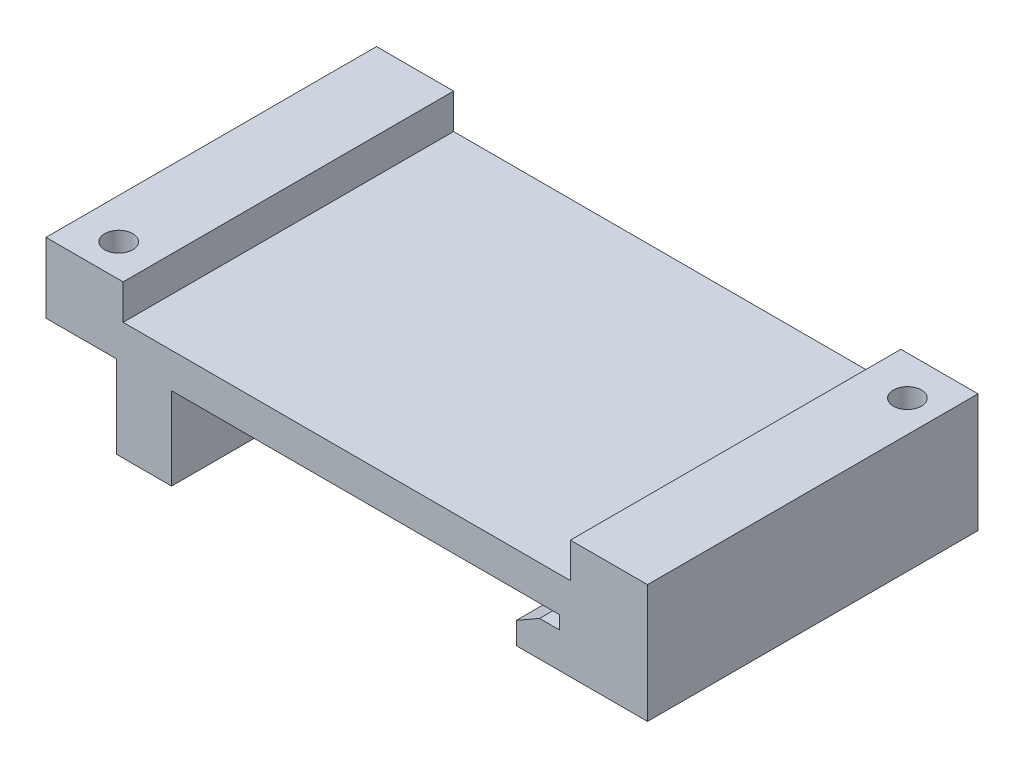
SolidWorks part; units mm, degrees
ref_plane "Front Plane" through (0, 0, 0) normal (0, 0, 1) x (1, 0, 0)
ref_plane "Top Plane" through (0, 0, 0) normal (0, 1, 0) x (1, 0, 0)
ref_plane "Right Plane" through (0, 0, 0) normal (1, 0, 0) x (0, 0, -1)
sketch "Sketch1" plane through (0, 0, 0) normal (0, 0, 1) x (1, 0, 0)
  line L0 (0, 0) -> (19.3, 0)
  line L1 (19.3, 0) -> (19.3, -1.2)
  line L2 (19.3, -1.2) -> (17.5, -1.2)
  line L3 (17.5, -1.2) -> (15.4, -2.4)
  line L4 (15.4, -2.4) -> (15.4, -4.4)
  line L5 (15.4, -4.4) -> (27.3, -4.4)
  line L8 (20.3, 3.175) -> (-20.3, 3.175)
  line L10 (-20.9, -7.5) -> (-15.9, -7.5)
  line L11 (-15.9, -7.5) -> (-15.9, 0)
  line L12 (-15.9, 0) -> (0, 0)
  line L14 (-27.3, 6.355) -> (-20.3, 6.355)
  line L15 (-20.3, 6.355) -> (-20.3, 3.175)
  line L16 (0, 0) -> (0, 6.355) construction
  line L18 (27.3, 6.355) -> (20.3, 6.355)
  line L19 (20.3, 6.355) -> (20.3, 3.175)
  line L20 (27.3, 6.355) -> (27.3, -4.4)
  line L21 (-27.3, 6.355) -> (-27.3, 0)
  line L22 (-27.3, 0) -> (-20.9, 0)
  line L23 (-20.9, 0) -> (-20.9, -7.5)
  dimension "D2" = 1.8
  dimension "D3" = 3.9
  dimension "D4" = 3.2
  dimension "D5" = 1.2
  dimension "D6" = 1.2
  dimension "D7" = 5
  dimension "D8" = 7.5
  dimension "D9" = 3.175
  dimension "D10" = 15.4
  dimension "D11" = 54.6
  dimension "D12" = 7
  dimension "D13" = 3.18
  dimension "D14" = 15.9
extrude "Boss-Extrude1" add sketch "Sketch1" along normal blind 30
sketch "Sketch2" plane through (-20.9, 0, 0) normal (-1, 0, 0) x (0, 0, 1)
  line L0 (15, 0) -> (15, -7.5) construction
  line L1 (30, 0) -> (0, 0) construction
  line L2 (30, -7.5) -> (0, -7.5) construction
  line L3 (0, 0) -> (15, 0) construction
  line L4 (7.5, 0) -> (7.5, -7.5) construction
  line L5 (15, 0) -> (30, 0) construction
  line L6 (22.5, 0) -> (22.5, -7.5) construction
  circle A0 centre (7.5, -3.75) radius 1.275
  circle A1 centre (22.5, -3.75) radius 1.275
  point P10 (15, -3.75)
  dimension "D1" = 2.55
extrude "Cut-Extrude1" cut sketch "Sketch2" against normal up to surface (5 mm away) up to face at (-15.9, -3.75, 15)
sketch "Sketch3" plane through (0, 6.355, 0) normal (0, 1, 0) x (1, 0, 0)
  line L1 (-27.3, -30) -> (-27.3, 0) construction
  line L2 (-20.3, -30) -> (-27.3, -30) construction
  line L3 (27.3, -30) -> (27.3, 0) construction
  line L4 (27.3, 0) -> (20.3, 0) construction
  circle A0 centre (-23.66, -27.04) radius 1.275
  circle A1 centre (24.43, -3.54) radius 1.275
  dimension "D3" = 2.55
  dimension "D1" = 3.64
  dimension "D2" = 2.96
  dimension "D4" = 2.87
  dimension "D5" = 3.54
extrude "Cut-Extrude2" cut sketch "Sketch3" against normal up to surface (3.18 mm away) up to face at (0, 3.175, 15)
